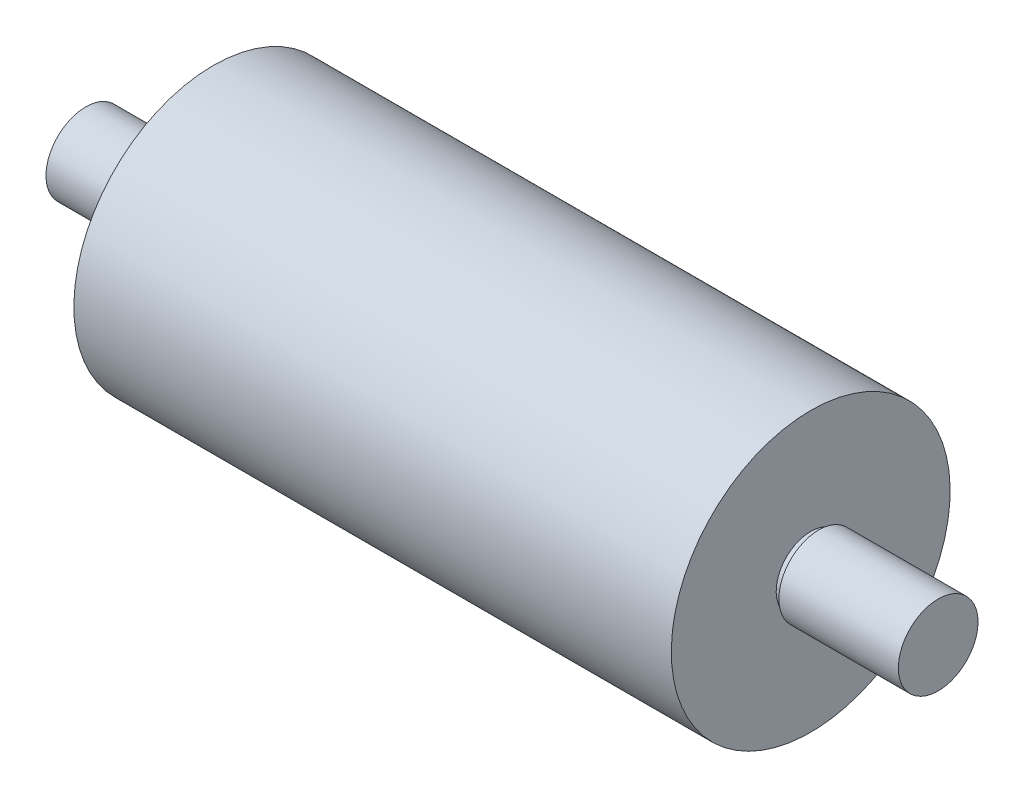
SolidWorks part; units mm, degrees
ref_plane "Plan de face" through (0, 0, 0) normal (0, 0, 1) x (1, 0, 0)
ref_plane "Plan de dessus" through (0, 0, 0) normal (0, 1, 0) x (1, 0, 0)
ref_plane "Plan de droite" through (0, 0, 0) normal (1, 0, 0) x (0, 0, -1)
sketch "Esquisse1" plane through (0, 0, 0) normal (0, 0, 1) x (1, 0, 0)
  line L0 (0, 0) -> (0, 100)
  line L1 (0, 100) -> (300, 100)
  line L2 (300, 100) -> (300, 74.3143)
  line L3 (300, 74.3143) -> (320, 74.3143)
  line L4 (320, 74.3143) -> (320, 350)
  line L5 (320, 350) -> (1820, 350)
  line L6 (1820, 350) -> (1820, 86.7213)
  line L7 (1820, 86.7213) -> (1840, 86.7213)
  line L8 (1840, 86.7213) -> (1840, 100)
  line L9 (1840, 100) -> (2140, 100)
  line L10 (2140, 100) -> (2140, 0)
  line L11 (2140, 0) -> (0, 0)
  dimension "D1" = 1500
  dimension "D2" = 300
  dimension "D3" = 20
  dimension "D4" = 20
  dimension "D5" = 300
  dimension "D6" = 350
  dimension "D7" = 100
  dimension "D8" = 100
revolve "Révolution1" add sketch "Esquisse1" angle 360 about L11 region at (1070.3206, 161.5132, 0)
